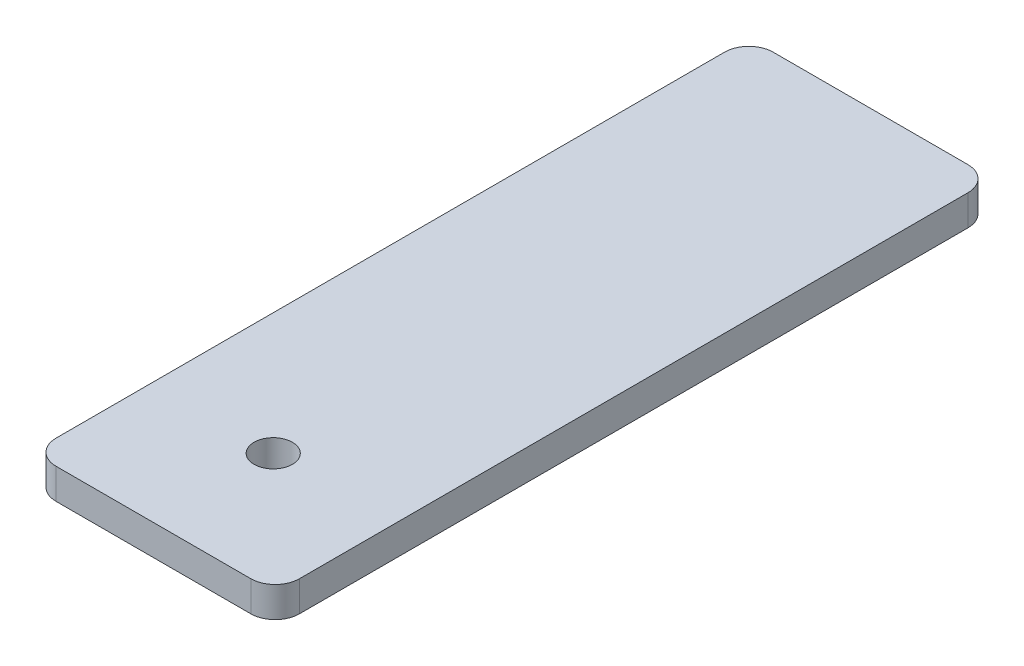
SolidWorks part; units mm, degrees
material "Acrylic (Medium-high impact)"
ref_plane "Front Plane" through (0, 0, 0) normal (0, 0, 1) x (1, 0, 0)
ref_plane "Top Plane" through (0, 0, 0) normal (0, 1, 0) x (1, 0, 0)
ref_plane "Right Plane" through (0, 0, 0) normal (1, 0, 0) x (0, 0, -1)
ref_plane "Plane1" through (0, 0, 0) normal (0, 1, 0) x (1, 0, 0)
sketch "Sketch1" plane through (0, 0, 0) normal (0, 1, 0) x (1, 0, 0)
  line L1 (-26.2811, -18.6088) -> (-0.8811, -18.6088)
  line L2 (-26.2811, -18.6088) -> (-26.2811, 56.2162)
  line L3 (-26.2811, 56.2162) -> (-0.8811, 56.2162)
  line L4 (-0.8811, -18.6088) -> (-0.8811, 56.2162)
  dimension "D1" = 74.825
  dimension "D2" = 25.4
extrude "Boss-Extrude1" add sketch "Sketch1" along normal blind 3.175
sketch "Sketch2" plane through (0, 3.175, 0) normal (0, 1, 0) x (1, 0, 0)
  line L0 (-26.2811, -18.6088) -> (-0.8811, -18.6088) construction
  line L1 (-26.2811, 56.2162) -> (-26.2811, -18.6088) construction
  circle A0 centre (-13.5811, -6.1088) radius 2
  dimension "D2" = 4
  dimension "D1" = 12.5
  dimension "D3" = 12.7
extrude "Cut-Extrude1" cut sketch "Sketch2" against normal through all
fillet "Fillet1" radius 2.54 4 edges at (-26.2811, 1.5875, -56.2162) (-0.8811, 1.5875, -56.2162) (-0.8811, 1.5875, 18.6088) (-26.2811, 1.5875, 18.6088)
